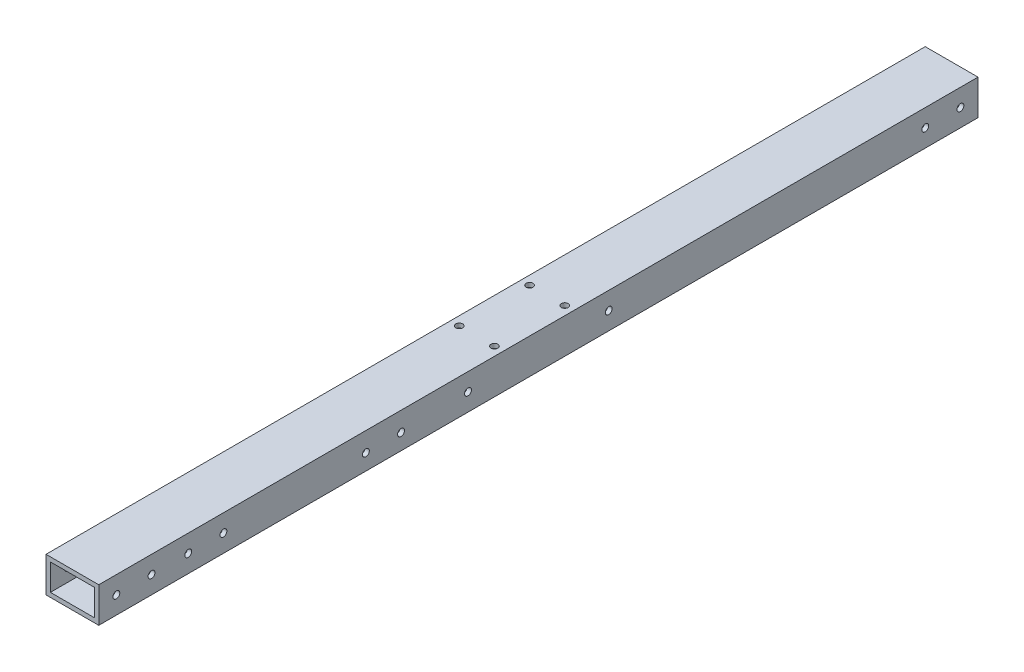
SolidWorks part; units mm, degrees
ref_plane "Front Plane" through (0, 0, 0) normal (0, 0, 1) x (1, 0, 0)
ref_plane "Top Plane" through (0, 0, 0) normal (0, 1, 0) x (1, 0, 0)
ref_plane "Right Plane" through (0, 0, 0) normal (1, 0, 0) x (0, 0, -1)
sketch "Sketch1" plane through (0, 0, 0) normal (0, 0, 1) x (1, 0, 0)
  line L0 (-15.875, 9.525) -> (15.875, 9.525)
  line L2 (-19.05, 12.7) -> (19.05, 12.7)
  line L3 (-19.05, 12.7) -> (-19.05, -12.7)
  line L4 (-19.05, -12.7) -> (19.05, -12.7)
  line L5 (19.05, 12.7) -> (19.05, -12.7)
  line L10 (15.875, 9.525) -> (15.875, -9.525)
  line L11 (-15.875, -9.525) -> (15.875, -9.525)
  line L12 (-15.875, 9.525) -> (-15.875, -9.525)
  point P12 (0, 12.7)
  point P14 (19.05, 0)
  dimension "Wall Thickness" = 3.175
  dimension "Outside Width" = 38.1
  dimension "Outside Height" = 25.4
  dimension "Inside Height" = 19.05
  dimension "Inside Width" = 31.75
sketch "Sketch2" plane through (0, 0, 0) normal (1, 0, 0) x (0, 0, -1)
  line L0 (317.5, 0) -> (-317.5, 0)
  point P4 (0, 0)
  point P7 (-317.5, 0)
  point P10 (317.5, 0)
  dimension "Length" = 635
sketch "Sketch3" plane through (0, 0, 0) normal (0, 0, 1) x (1, 0, 0)
  line L21 (19.05, 12.7) -> (-19.05, 12.7)
  line L22 (19.05, -12.7) -> (19.05, 12.7)
  line L23 (-19.05, -12.7) -> (19.05, -12.7)
  line L24 (-19.05, 12.7) -> (-19.05, -12.7)
  line L25 (19.05, 12.7) -> (-19.05, 12.7)
  line L26 (19.05, -12.7) -> (19.05, 12.7)
  line L27 (-19.05, -12.7) -> (19.05, -12.7)
  line L28 (-19.05, 12.7) -> (-19.05, -12.7)
  line L29 (15.875, 9.525) -> (-15.875, 9.525)
  line L30 (15.875, -9.525) -> (15.875, 9.525)
  line L31 (-15.875, -9.525) -> (15.875, -9.525)
  line L32 (-15.875, 9.525) -> (-15.875, -9.525)
  line L33 (15.875, 9.525) -> (-15.875, 9.525)
  line L34 (15.875, -9.525) -> (15.875, 9.525)
  line L35 (-15.875, -9.525) -> (15.875, -9.525)
  line L36 (-15.875, 9.525) -> (-15.875, -9.525)
  dimension "D1" = 0
  dimension "D2" = 0
extrude "Boss-Extrude1" add sketch "Sketch3" along normal up to vertex (317.5 mm away) and the other way up to vertex (317.5 mm away) up to point (0, 0, 317.5) other way up to point (0, 0, -317.5)
sketch "Drawing Reference" plane through (0, 0, 0) normal (1, 0, 0) x (0, 0, -1)
  line L0 (-317.5, 0) -> (317.5, 0) construction
  line L1 (0, -12.7) -> (0, 12.7) construction
  line L2 (-317.5, -12.7) -> (317.5, -12.7) construction
  line L5 (-317.5, 12.7) -> (317.5, 12.7) construction
  point P7 (-290.068, 0)
  point P8 (290.068, 0)
  dimension "D1" = 27.432
sketch "Sketch4" plane through (-19.05, 0, 0) normal (-1, 0, 0) x (0, 0, 1)
  line L0 (-317.5, 0) -> (-304.8, 0)
  line L1 (-317.5, 12.7) -> (-317.5, -12.7) construction
  line L2 (-304.8, 0) -> (-279.4, 0)
  line L3 (317.5, 12.7) -> (317.5, -12.7) construction
  line L4 (317.5, 0) -> (304.8, 0)
  line L5 (304.8, 0) -> (279.4, 0)
  line L6 (0, 0) -> (50.8, 0) construction
  line L7 (0, 0) -> (-50.8, 0) construction
  point P11 (-304.8, 0)
  point P13 (-279.4, 0)
  point P14 (304.8, 0)
  point P15 (279.4, 0)
hole_wizard "#10 Clearance Hole2" positions "Sketch11" profile "Sketch12" hole size "#10" standard "ANSI Inch" end condition through all
sketch "Sketch11" plane through (-19.05, 0, 0) normal (-1, 0, 0) x (0, 0, 1)
  point P0 (-304.8, 0)
  point P3 (-279.4, 0)
  point P6 (279.4, 0)
  point P9 (304.8, 0)
sketch "Sketch12" plane through (-19.05, 0, -304.8) normal (0, 1, 0) x (0, 0, 1)
  line L0 (0, 0) -> (0, 38.1)
  line L1 (0, 38.1) -> (2.4892, 38.1)
  line L2 (2.4892, 38.1) -> (2.4892, 0)
  line L5 (2.4892, 0) -> (0, 0)
  line L11 (0, -6.35) -> (0, 107.95) construction
  dimension "Thru Hole Dia." = 4.9784
  dimension "Thru Hole Depth" = 38.1
hole_wizard "#10 Clearance Hole5" positions "Sketch14" profile "Sketch16" hole size "#10" standard "ANSI Inch" end condition through all
sketch "Sketch14" plane through (19.05, 0, 0) normal (1, 0, 0) x (0, 0, -1)
  point P10 (-124.587, -1.2316)
  point P13 (-99.187, -1.2316)
  point P17 (-252.857, 0)
  point P20 (-227.457, 0)
sketch "Sketch16" plane through (19.05, -1.2316, 124.587) normal (0, 1, 0) x (0, 0, -1)
  line L0 (0, 0) -> (0, 38.1)
  line L1 (0, 38.1) -> (2.4892, 38.1)
  line L2 (2.4892, 38.1) -> (2.4892, 0)
  line L5 (2.4892, 0) -> (0, 0)
  line L11 (0, -6.35) -> (0, 107.95) construction
  dimension "Thru Hole Dia." = 4.9784
  dimension "Thru Hole Depth" = 38.1
sketch "Sketch17" plane through (19.05, 0, 0) normal (1, 0, 0) x (0, 0, -1)
  point P0 (-252.857, 0)
  point P1 (-227.457, 0)
hole_wizard "#10 Clearance Hole4" positions "Sketch18" profile "Sketch19" hole size "#10" standard "ANSI Inch" end condition through all
sketch "Sketch18" plane through (19.05, 0, 0) normal (1, 0, 0) x (0, 0, -1)
  point P0 (-252.857, 0)
  point P3 (-227.457, 0)
sketch "Sketch19" plane through (19.05, 0, 252.857) normal (0, 1, 0) x (0, 0, -1)
  line L0 (0, 0) -> (0, 38.1)
  line L1 (0, 38.1) -> (2.4892, 38.1)
  line L2 (2.4892, 38.1) -> (2.4892, 0)
  line L5 (2.4892, 0) -> (0, 0)
  line L11 (0, -6.35) -> (0, 107.95) construction
  dimension "Thru Hole Dia." = 4.9784
  dimension "Thru Hole Depth" = 38.1
hole_wizard "#10 Clearance Hole3" positions "Sketch20" profile "Sketch21" hole size "#10" standard "ANSI Inch" end condition through all
sketch "Sketch20" plane through (-19.05, 0, 0) normal (-1, 0, 0) x (0, 0, 1)
  point P0 (-50.8, 0)
  point P3 (50.8, 0)
sketch "Sketch21" plane through (-19.05, 0, -50.8) normal (0, 1, 0) x (0, 0, 1)
  line L0 (0, 0) -> (0, 38.1)
  line L1 (0, 38.1) -> (2.4892, 38.1)
  line L2 (2.4892, 38.1) -> (2.4892, 0)
  line L5 (2.4892, 0) -> (0, 0)
  line L11 (0, -6.35) -> (0, 107.95) construction
  dimension "Thru Hole Dia." = 4.9784
  dimension "Thru Hole Depth" = 38.1
sketch "Sketch22" plane through (0, 12.7, 0) normal (0, 1, 0) x (1, 0, 0)
  line L0 (19.05, 0) -> (12.7, 0) construction
  line L1 (19.05, -317.5) -> (19.05, 317.5) construction
  line L2 (12.7, -25.4) -> (12.7, 25.4) construction
  line L3 (-12.7, -25.4) -> (-12.7, 25.4) construction
  point P8 (12.7, 0)
  dimension "D1" = 25.4
hole_wizard "#10 Clearance Hole6" positions "Sketch25" profile "Sketch26" hole size "#10" standard "ANSI Inch" end condition through all
sketch "Sketch25" plane through (0, 12.7, 0) normal (0, 1, 0) x (1, 0, 0)
  point P0 (12.7, -25.4)
  point P3 (-12.7, -25.4)
  point P6 (12.7, 25.4)
  point P9 (-12.7, 25.4)
sketch "Sketch26" plane through (12.7, 12.7, 25.4) normal (1, 0, 0) x (0, 0, 1)
  line L0 (0, 0) -> (0, 25.4)
  line L1 (0, 25.4) -> (5.2197, 25.4)
  line L2 (2.4892, 22.2589) -> (2.4892, 0)
  line L5 (2.4892, 0) -> (0, 0)
  line L7 (5.2197, 25.4) -> (2.4892, 22.2589)
  line L8 (-5.2197, 25.4) -> (-2.4892, 22.2589) construction
  line L11 (0, -6.35) -> (0, 107.95) construction
  dimension "Thru Hole Dia." = 4.9784
  dimension "Thru Hole Depth" = 25.4
  dimension "Far C'Sink Dia." = 10.4394
  dimension "Far C'Sink Angle" = 82
equation "\"D1@Drawing Reference\"=\"Outside Width@Sketch1\" * 0.72"
